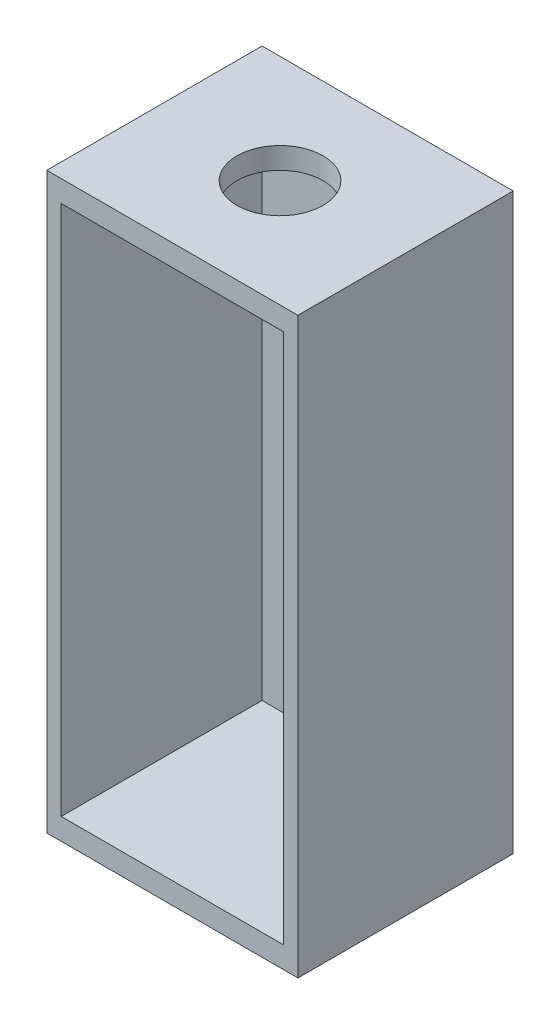
SolidWorks part; units mm, degrees
ref_plane "Front Plane" through (0, 0, 0) normal (0, 0, 1) x (1, 0, 0)
ref_plane "Top Plane" through (0, 0, 0) normal (0, 1, 0) x (1, 0, 0)
ref_plane "Right Plane" through (0, 0, 0) normal (1, 0, 0) x (0, 0, -1)
sketch "Sketch1" plane through (0, 0, 0) normal (0, 0, 1) x (1, 0, 0)
  line L1 (17.5, -40) -> (-17.5, -40)
  line L2 (17.5, -40) -> (17.5, 40)
  line L3 (17.5, 40) -> (-17.5, 40)
  line L4 (-17.5, -40) -> (-17.5, 40)
  line L5 (17.5, -40) -> (-17.5, 40) construction
  line L6 (17.5, 40) -> (-17.5, -40) construction
  point P0 (0, 0)
  dimension "D1" = 35
  dimension "D2" = 80
extrude "Boss-Extrude1" add sketch "Sketch1" along normal blind 30
sketch "Sketch2" plane through (0, 0, 30) normal (0, 0, 1) x (1, 0, 0)
  line L4 (-17.5, 40) -> (-17.5, -40)
  line L5 (-17.5, -40) -> (17.5, -40)
  line L6 (17.5, -40) -> (17.5, 40)
  line L7 (17.5, 40) -> (-17.5, 40)
  line L8 (-17.5, 40) -> (-17.5, -40)
  line L9 (-17.5, -40) -> (17.5, -40)
  line L10 (17.5, -40) -> (17.5, 40)
  line L11 (17.5, 40) -> (-17.5, 40)
  line L13 (15.5, -37) -> (-15.5, -37)
  line L14 (15.5, -37) -> (15.5, 37)
  line L15 (15.5, 37) -> (-15.5, 37)
  line L16 (-15.5, -37) -> (-15.5, 37)
  line L17 (15.5, -37) -> (-15.5, 37) construction
  line L18 (15.5, 37) -> (-15.5, -37) construction
  point P2 (0, 0)
  dimension "D2" = 2
  dimension "D3" = 3
  dimension "D1" = 0
extrude "Cut-Extrude1" cut sketch "Sketch2" against normal offset from surface (28 mm away) 2 contours L16 L13 L14 L15 region at (0, 0, 30) up to face at (0, 0, 0)
sketch "Sketch3" plane through (0, 40, 0) normal (0, 1, 0) x (1, 0, 0)
  line L0 (0, 0) -> (0, -30)
  line L1 (-17.5, -15) -> (17.5, -15)
  line L4 (17.5, 0) -> (-17.5, 0)
  line L5 (-17.5, 0) -> (-17.5, -30)
  line L6 (-17.5, -30) -> (17.5, -30)
  line L7 (17.5, -30) -> (17.5, 0)
  line L8 (17.5, 0) -> (-17.5, 0)
  line L9 (-17.5, 0) -> (-17.5, -30)
  line L10 (-17.5, -30) -> (17.5, -30)
  line L11 (17.5, -30) -> (17.5, 0)
  circle A0 centre (0, -15) radius 6
  dimension "D2" = 12
  dimension "D1" = 0
extrude "Cut-Extrude2" cut sketch "Sketch3" against normal blind 3 contours L0 A0 L1 | L1 A0 L0 | L0 A0 L1 | L1 A0 L0 region at (2.5465, 40, 12.4535) region at (-2.5465, 40, 12.4535) region at (2.5465, 40, 17.5465) region at (-2.5465, 40, 17.5465)
sketch "Sketch4" plane through (0, 0, 0) normal (0, 0, -1) x (-1, 0, 0)
  line L0 (0, 40) -> (0, -5)
  line L4 (17.5, -40) -> (17.5, 40)
  line L5 (17.5, 40) -> (-17.5, 40)
  line L6 (-17.5, 40) -> (-17.5, -40)
  line L7 (-17.5, -40) -> (17.5, -40)
  line L8 (17.5, -40) -> (17.5, 40)
  line L9 (17.5, 40) -> (-17.5, 40)
  line L10 (-17.5, 40) -> (-17.5, -40)
  line L11 (-17.5, -40) -> (17.5, -40)
  circle A0 centre (0, -5) radius 4.5
  dimension "D3" = 9
  dimension "D2" = 45
  dimension "D1" = 0
extrude "Cut-Extrude3" cut sketch "Sketch4" against normal blind 3 contours A0 region at (-3.092, -1.908, 0)
